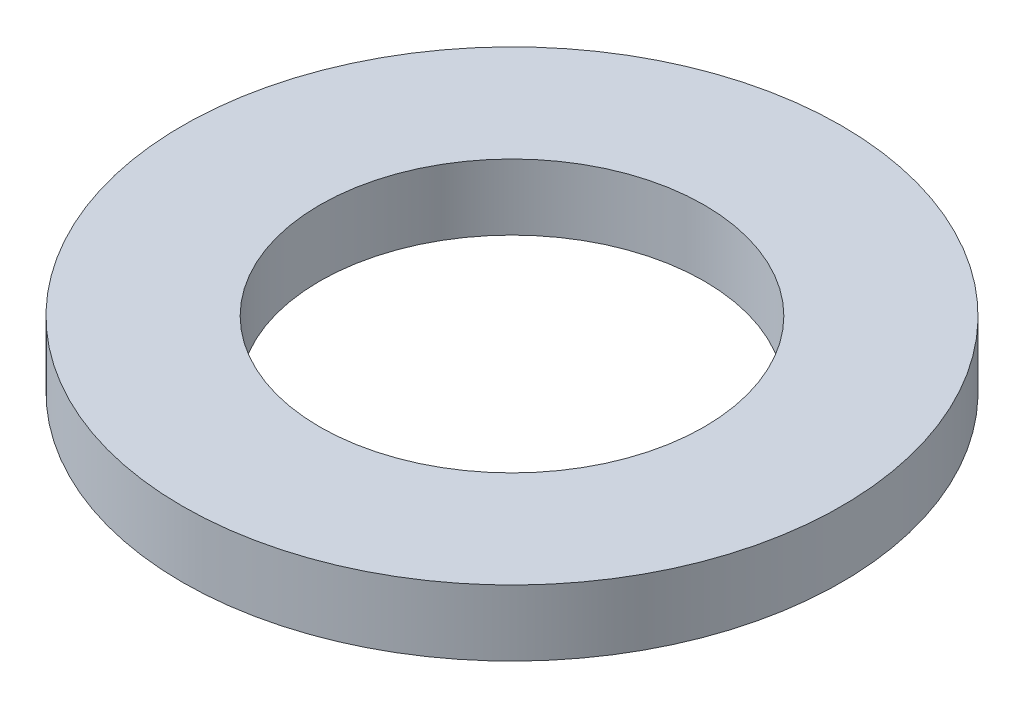
SolidWorks part; units mm, degrees
ref_plane "Front Plane" through (0, 0, 0) normal (0, 0, 1) x (1, 0, 0)
ref_plane "Top Plane" through (0, 0, 0) normal (0, 1, 0) x (1, 0, 0)
ref_plane "Right Plane" through (0, 0, 0) normal (1, 0, 0) x (0, 0, -1)
sketch "Sketch1" plane through (0, 0, 0) normal (0, 1, 0) x (1, 0, 0)
  circle A0 centre (0, 0) radius 60
  dimension "FLANGE_OD" = 120
extrude "Boss-Extrude1" add sketch "Sketch1" along normal blind 12
sketch "Sketch2" plane through (0, 0, 0) normal (0, 1, 0) x (1, 0, 0)
  circle A0 centre (0, 0) radius 35
  dimension "BORE_D" = 70
extrude "Cut-Extrude1" cut sketch "Sketch2" along normal through all
sketch "Sketch3" plane through (0, 12, 0) normal (0, 1, 0) x (1, 0, 0)
  circle A0 centre (0, 0) radius 26.7103 construction
  circle A1 centre (-26.7103, 0) radius 3.9339
  dimension "BOLT_D" = 7.8678
  dimension "BOLT_PCD" = 53.4207
extrude "Cut-Extrude2" cut sketch "Sketch3" against normal blind 7.8453 rebuild error yes
pattern_circular "CirPattern1" count 4 over 360 rebuild error yes
